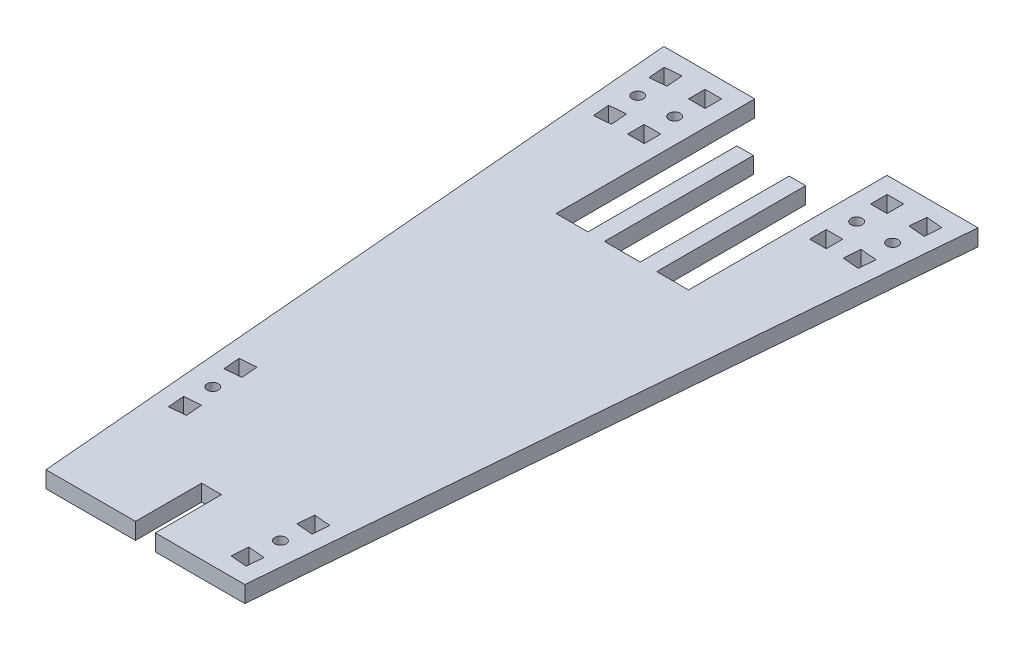
SolidWorks part; units mm, degrees
ref_plane "Front Plane" through (0, 0, 0) normal (0, 0, 1) x (1, 0, 0)
ref_plane "Top Plane" through (0, 0, 0) normal (0, 1, 0) x (1, 0, 0)
ref_plane "Right Plane" through (0, 0, 0) normal (1, 0, 0) x (0, 0, -1)
sketch "Sketch1" plane through (0, 0, 0) normal (0, 1, 0) x (1, 0, 0)
  line L0 (0, 0) -> (0, -183.008) construction
  line L1 (-47.5292, 76.2) -> (-25.4, 76.2)
  line L2 (47.5292, 76.2) -> (25.4, -183.008) construction
  line L3 (-47.5292, 76.2) -> (-25.4, -183.008) construction
  line L4 (38.1, 40.132) -> (44.45, 40.132) construction
  line L5 (-47.5292, 76.2) -> (-60.2754, 76.2)
  line L6 (-3.81, -183.008) -> (-3.81, -157.608)
  line L7 (-57.15, 0) -> (57.15, 0) construction
  line L8 (31.75, 76.2) -> (31.75, 40.132) construction
  line L9 (-31.75, 76.2) -> (-31.75, 40.132) construction
  line L10 (6.858, 57.15) -> (6.858, 0) construction
  line L11 (-6.858, 57.15) -> (-6.858, 0) construction
  line L12 (-6.858, 57.15) -> (-6.858, 0)
  line L13 (-6.858, 0) -> (6.858, 0)
  line L14 (6.858, 0) -> (6.858, 57.15)
  line L15 (6.858, 57.15) -> (13.208, 57.15)
  line L16 (-3.81, -157.608) -> (3.81, -157.608)
  line L17 (3.81, -183.008) -> (3.81, -157.608)
  line L18 (13.208, 57.15) -> (13.208, 0)
  line L19 (13.208, 0) -> (25.4, 0)
  line L20 (25.4, 0) -> (25.4, 76.2)
  line L21 (25.4, 76.2) -> (47.5292, 76.2)
  line L22 (-25.4, 0) -> (-25.4, 76.2)
  line L23 (-13.208, 0) -> (-25.4, 0)
  line L24 (-13.208, 57.15) -> (-13.208, 0)
  line L25 (-6.858, 0) -> (-6.858, 57.15)
  line L26 (-13.208, 57.15) -> (-6.858, 57.15)
  line L27 (-3.81, -183.008) -> (3.81, -157.608) construction
  line L28 (-3.81, -157.608) -> (3.81, -183.008) construction
  line L29 (47.5292, 76.2) -> (60.2754, 76.2)
  line L30 (60.2754, 76.2) -> (38.1462, -183.008)
  line L31 (-25.4, -183.008) -> (-3.81, -183.008)
  line L32 (3.81, -183.008) -> (25.4, -183.008)
  line L33 (25.4, -183.008) -> (38.1462, -183.008)
  line L34 (-60.2754, 76.2) -> (-38.1462, -183.008)
  line L35 (-25.4, -183.008) -> (-38.1462, -183.008)
  line L36 (-35.0258, -144.908) -> (-28.6988, -144.3678) construction
  line L37 (31.7731, -183.008) -> (25.4461, -182.4678) construction
  line L38 (32.3132, -176.681) -> (31.7731, -183.008) construction
  line L39 (-35.5659, -138.581) -> (-35.0258, -144.908) construction
  point P0 (0, 0)
  point P15 (0, -170.308)
  line B0 (34.925, 40.132) -> (34.925, 69.85) construction
  line B1 (32.766, 54.991) -> (37.084, 54.991) construction
  line B2 (31.75, 63.5) -> (38.1, 63.5)
  line B3 (31.75, 63.5) -> (31.75, 69.85)
  line B4 (31.75, 69.85) -> (38.1, 69.85)
  line B5 (38.1, 63.5) -> (38.1, 69.85)
  line B6 (31.75, 63.5) -> (38.1, 69.85) construction
  line B7 (31.75, 69.85) -> (38.1, 63.5) construction
  line B8 (31.75, 40.132) -> (38.1, 46.482) construction
  line B9 (31.75, 46.482) -> (38.1, 40.132) construction
  line B10 (38.1, 46.482) -> (38.1, 40.132)
  line B11 (31.75, 40.132) -> (38.1, 40.132)
  line B12 (31.75, 46.482) -> (31.75, 40.132)
  line B13 (31.75, 46.482) -> (38.1, 46.482)
  circle B14 centre (34.925, 54.991) radius 2.159
  line B15 (-34.925, 40.132) -> (-34.925, 69.85) construction
  line B16 (-32.766, 54.991) -> (-37.084, 54.991) construction
  line B17 (-31.75, 63.5) -> (-38.1, 63.5)
  line B18 (-31.75, 63.5) -> (-31.75, 69.85)
  line B19 (-31.75, 69.85) -> (-38.1, 69.85)
  line B20 (-38.1, 63.5) -> (-38.1, 69.85)
  line B21 (-31.75, 63.5) -> (-38.1, 69.85) construction
  line B22 (-31.75, 69.85) -> (-38.1, 63.5) construction
  line B23 (-31.75, 40.132) -> (-38.1, 46.482) construction
  line B24 (-31.75, 46.482) -> (-38.1, 40.132) construction
  line B25 (-38.1, 46.482) -> (-38.1, 40.132)
  line B26 (-31.75, 40.132) -> (-38.1, 40.132)
  line B27 (-31.75, 46.482) -> (-31.75, 40.132)
  line B28 (-31.75, 46.482) -> (-38.1, 46.482)
  circle B29 centre (-34.925, 54.991) radius 2.159
  line B30 (47.6247, 39.9927) -> (50.1526, 69.6029) construction
  line B31 (46.7374, 54.9814) -> (51.0398, 54.6141) construction
  line B32 (46.4489, 63.546) -> (52.7759, 63.0059)
  line B33 (46.4489, 63.546) -> (46.9891, 69.873)
  line B34 (46.9891, 69.873) -> (53.316, 69.3329)
  line B35 (52.7759, 63.0059) -> (53.316, 69.3329)
  line B36 (46.4489, 63.546) -> (53.316, 69.3329) construction
  line B37 (46.9891, 69.873) -> (52.7759, 63.0059) construction
  line B38 (44.4612, 40.2627) -> (51.3283, 46.0496) construction
  line B39 (45.0013, 46.5897) -> (50.7881, 39.7226) construction
  line B40 (51.3283, 46.0496) -> (50.7881, 39.7226)
  line B41 (44.4612, 40.2627) -> (50.7881, 39.7226)
  line B42 (45.0013, 46.5897) -> (44.4612, 40.2627)
  line B43 (45.0013, 46.5897) -> (51.3283, 46.0496)
  circle B44 centre (48.8886, 54.7978) radius 2.159
  line B45 (29.1498, -176.4109) -> (31.6777, -146.8006) construction
  line B46 (28.2625, -161.4221) -> (32.5649, -161.7894) construction
  line B47 (27.974, -152.8575) -> (34.301, -153.3977)
  line B48 (27.974, -152.8575) -> (28.5142, -146.5305)
  line B49 (28.5142, -146.5305) -> (34.8412, -147.0707)
  line B50 (34.301, -153.3977) -> (34.8412, -147.0707)
  line B51 (27.974, -152.8575) -> (34.8412, -147.0707) construction
  line B52 (28.5142, -146.5305) -> (34.301, -153.3977) construction
  line B53 (25.9863, -176.1408) -> (32.8534, -170.354) construction
  line B54 (26.5264, -169.8138) -> (32.3132, -176.681) construction
  line B55 (32.8534, -170.354) -> (32.3132, -176.681)
  line B56 (25.9863, -176.1408) -> (32.3132, -176.681)
  line B57 (26.5264, -169.8138) -> (25.9863, -176.1408)
  line B58 (26.5264, -169.8138) -> (32.8534, -170.354)
  circle B59 centre (30.4137, -161.6057) radius 2.159
  line B60 (-32.4024, -138.3109) -> (-34.9303, -108.7006) construction
  line B61 (-31.5152, -123.3221) -> (-35.8176, -123.6894) construction
  line B62 (-31.2267, -114.7575) -> (-37.5537, -115.2977)
  line B63 (-31.2267, -114.7575) -> (-31.7669, -108.4305)
  line B64 (-31.7669, -108.4305) -> (-38.0938, -108.9707)
  line B65 (-37.5537, -115.2977) -> (-38.0938, -108.9707)
  line B66 (-31.2267, -114.7575) -> (-38.0938, -108.9707) construction
  line B67 (-31.7669, -108.4305) -> (-37.5537, -115.2977) construction
  line B68 (-29.239, -138.0408) -> (-36.1061, -132.254) construction
  line B69 (-29.7791, -131.7138) -> (-35.5659, -138.581) construction
  line B70 (-36.1061, -132.254) -> (-35.5659, -138.581)
  line B71 (-29.239, -138.0408) -> (-35.5659, -138.581)
  line B72 (-29.7791, -131.7138) -> (-29.239, -138.0408)
  line B73 (-29.7791, -131.7138) -> (-36.1061, -132.254)
  circle B74 centre (-33.6664, -123.5057) radius 2.159
  line B75 (-47.6247, 39.9927) -> (-50.1526, 69.6029) construction
  line B76 (-46.7374, 54.9814) -> (-51.0398, 54.6141) construction
  line B77 (-46.4489, 63.546) -> (-52.7759, 63.0059)
  line B78 (-46.4489, 63.546) -> (-46.9891, 69.873)
  line B79 (-46.9891, 69.873) -> (-53.316, 69.3329)
  line B80 (-52.7759, 63.0059) -> (-53.316, 69.3329)
  line B81 (-46.4489, 63.546) -> (-53.316, 69.3329) construction
  line B82 (-46.9891, 69.873) -> (-52.7759, 63.0059) construction
  line B83 (-44.4612, 40.2627) -> (-51.3283, 46.0496) construction
  line B84 (-45.0013, 46.5897) -> (-50.7881, 39.7226) construction
  line B85 (-51.3283, 46.0496) -> (-50.7881, 39.7226)
  line B86 (-44.4612, 40.2627) -> (-50.7881, 39.7226)
  line B87 (-45.0013, 46.5897) -> (-44.4612, 40.2627)
  line B88 (-45.0013, 46.5897) -> (-51.3283, 46.0496)
  circle B89 centre (-48.8886, 54.7978) radius 2.159
  dimension "D1" = 63.5
  dimension "D2" = 6.35
  dimension "D3" = 6.858
  dimension "D4" = 50.8
  dimension "D5" = 25.4
  dimension "D6" = 7.62
  dimension "D7" = 19.05
  dimension "D8" = 259.208
  dimension "D9" = 6.35
  dimension "D10" = 6.35
  dimension "D11" = 6.35
  dimension "D12" = 76.2
  dimension "D13" = 6.35
  dimension "D14" = 6.35
  dimension "D15" = 38.1
  dimension "D16" = 183.008
  dimension "D17" = 149.2341
  dimension "D18" = 187.4727
sketch_block_instance "Female T-Slot Assembly-1"
sketch_block "Female T-Slot Assembly" parameters "D4"=4.318, "D1"=6.35, "D2"=6.35, "D3"=6.35
sketch_block_instance "Female T-Slot Assembly-3"
sketch_block_instance "Female T-Slot Assembly-1"
sketch_block_instance "Female T-Slot Assembly-14"
sketch_block_instance "Female T-Slot Assembly-16"
sketch_block_instance "Female T-Slot Assembly-17"
extrude "Boss-Extrude1" add sketch "Sketch1" along normal blind 6.35 contours L26 L24 L23 L22 L1 L21 L20 L19 L18 L15 L14 L13 L12 B29 B28 B27 B26 B25 B12 B13 B10 B11 B5 B2 B3 region at (0.0143, 0, 55.6522)
equation "\"Ball Diameter\"= 1.75in"
equation "\"Ball Radius\" = \"Ball Diameter\"/2"
equation "\"Sheet Thickness\"= 0.25in"
equation "\"Screw Diameter\"= .17in"
equation "\"Robot Diameter\"= 14in"
equation "\"Castor Screw Diameter\"= 0.22in"
equation "\"Wheel Diameter\" = 4in"
equation "\"Nut Diameter\" = 8.4mm"
equation "\"Nut Height\" = 2.9mm"
equation "\"Screw Height\" = 0.55in"
equation "\"Pulley Diameter\" = 1in"
equation "\"Reactor Height\" = 14in"
equation "\"Elevator Height\" = 11.5in"
equation "\"Elevator Width\" = \"Ball Diameter\" + 0.25in"
equation "\"Elevator Bearing Diameter\" = sqr(2*(\"Sheet Thickness\"^2)) + 0.2in"
equation "\"Elevator Axle Endcap Diameter\" = \"Pulley Diameter\" + 0.25in"
equation "\"Elevator Axle Length\" = \"Elevator Width\" + 8*\"Sheet Thickness\""
equation "\"Elevator Clearance from Axis\" = 3.28in"
equation "\"Elevator Horizontal Clearance\" = \"Elevator Width\" + 0.5in"
equation "\"Claw Horizontal Seperation\" = (\"Elevator Width\"/2) - (1.5 * \"Sheet Thickness\") - 0.15in"
equation "\"Claw Radius\" = \"Ball Radius\" + 0.1in"
equation "\"Castor Wheel Height\" = 1.25in"
equation "\"Length of Chute\" = 8in"
equation "\"D4@Sketch1\"=\"Ball Diameter\" + 0.25in"
equation "\"D8@Sketch1\"=(7in+5in-1.95in)/cos(10deg)"
